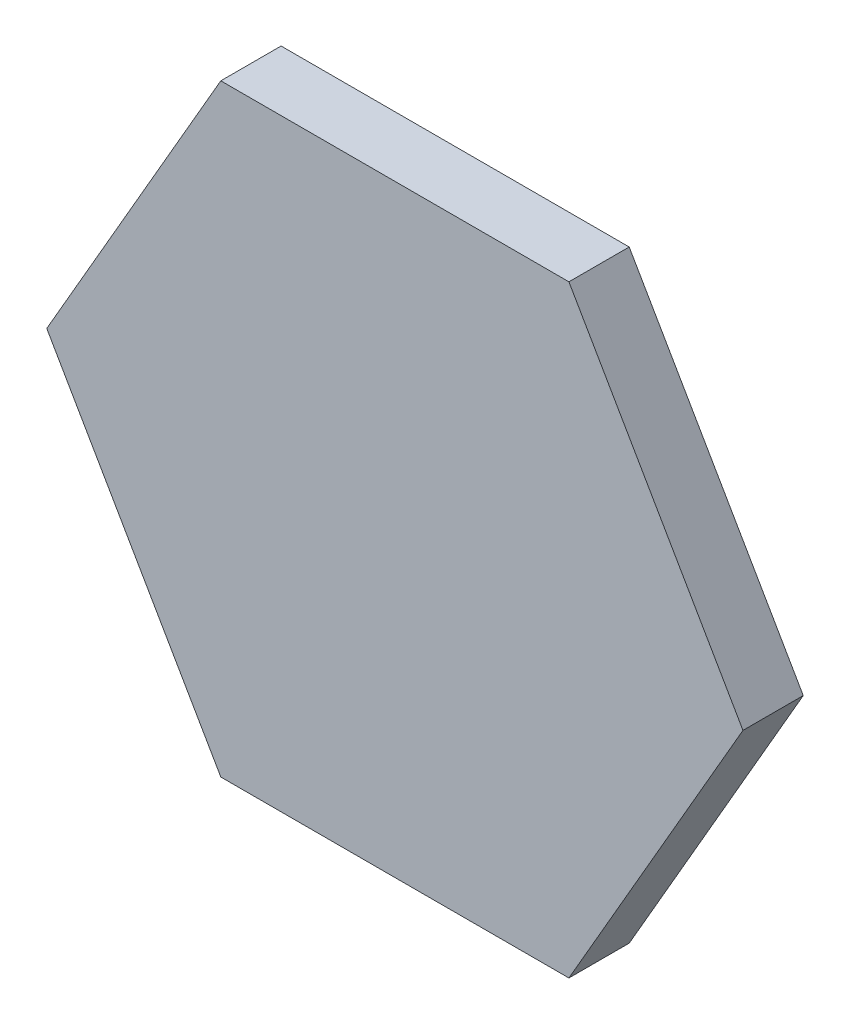
SolidWorks part; units mm, degrees
ref_plane "Front Plane" through (0, 0, 0) normal (0, 0, 1) x (1, 0, 0)
ref_plane "Top Plane" through (0, 0, 0) normal (0, 1, 0) x (1, 0, 0)
ref_plane "Right Plane" through (0, 0, 0) normal (1, 0, 0) x (0, 0, -1)
sketch "Sketch1" plane through (0, 0, 0) normal (0, 0, 1) x (1, 0, 0)
  line L1 (57.735, 0) -> (28.8675, 50)
  line L2 (28.8675, 50) -> (-28.8675, 50)
  line L3 (-28.8675, 50) -> (-57.735, 0)
  line L4 (-57.735, 0) -> (-28.8675, -50)
  line L5 (-28.8675, -50) -> (28.8675, -50)
  line L6 (28.8675, -50) -> (57.735, 0)
  circle A0 centre (0, 0) radius 50 construction
  dimension "D1" = 100
extrude "Boss-Extrude1" add sketch "Sketch1" along normal mid plane 10
sketch "Sketch2" plane through (0, 0, -5) normal (0, 0, -1) x (-1, 0, 0)
  line L0 (0, 0) -> (-28.8675, -50) construction
  line L1 (28.8675, -50) -> (-28.8675, -50) construction
  line L2 (-28.8675, -50) -> (-57.735, 0) construction
  line L3 (-57.735, 0) -> (-28.8675, 50) construction
  circle A0 centre (-20.2073, -35) radius 9
  circle A1 centre (-40.4145, 0) radius 9
  circle A2 centre (-20.2073, 35) radius 9
  circle A3 centre (20.2073, 35) radius 9
  circle A4 centre (40.4145, 0) radius 9
  circle A5 centre (20.2073, -35) radius 9
  point P20 (0, 0)
  dimension "D1" = 18
  dimension "D2" = 15
  dimension "D3" = 6
  dimension "D4" = 15
  dimension "D5" = 15
extrude "Cut-Extrude1" cut sketch "Sketch2" against normal blind 5
